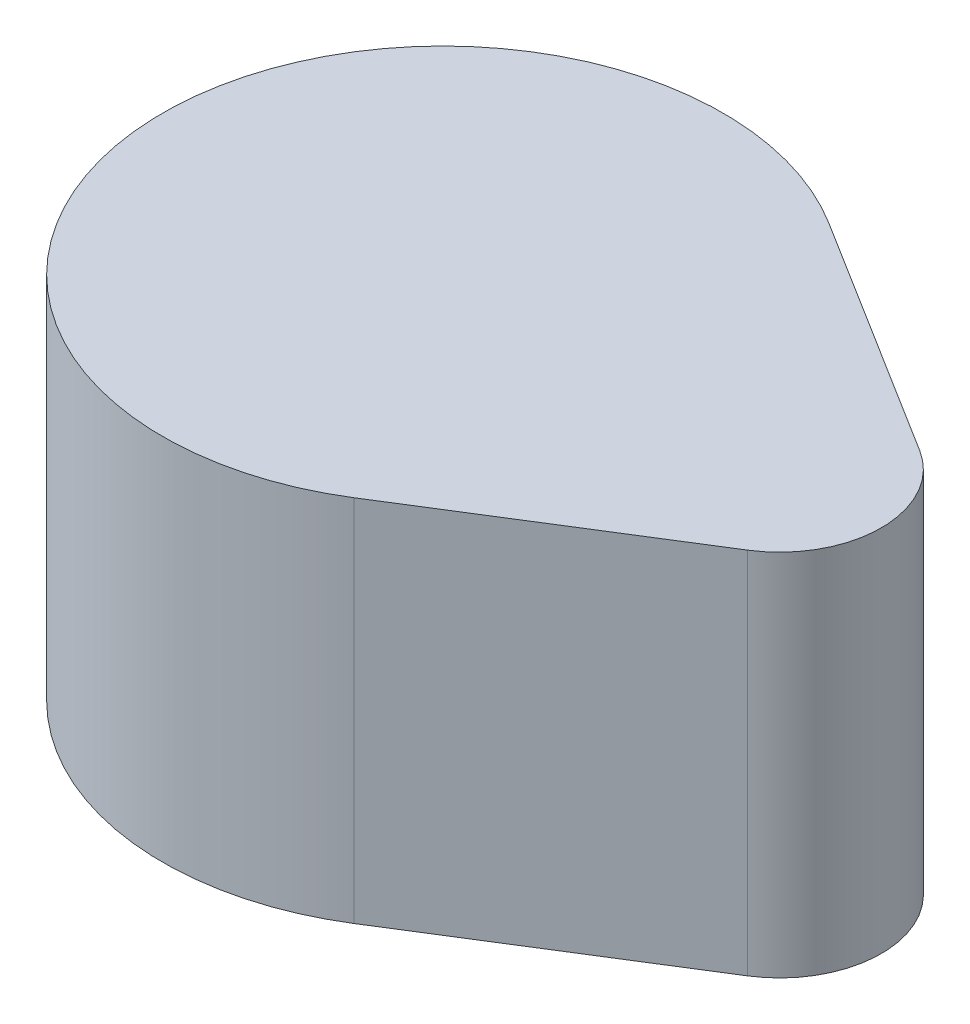
SolidWorks part; units mm, degrees
ref_plane "Front Plane" through (0, 0, 0) normal (0, 0, 1) x (1, 0, 0)
ref_plane "Top Plane" through (0, 0, 0) normal (0, 1, 0) x (1, 0, 0)
ref_plane "Right Plane" through (0, 0, 0) normal (1, 0, 0) x (0, 0, -1)
sketch "Sketch1" plane through (0, 0, 0) normal (0, 1, 0) x (1, 0, 0)
  line L0 (5.1162, 8.1821) -> (13.4556, 2.9676)
  line L1 (5.1162, -8.1821) -> (13.4556, -2.9676)
  line L3 (-9.65, 0) -> (-9.65, -24.75) construction
  line L4 (-9.65, -24.75) -> (15.1, -24.75) construction
  line L5 (15.1, -24.75) -> (15.1, 0) construction
  arc A0 (5.1162, 8.1821) -> (5.1162, -8.1821) centre (0, 0) ccw
  arc A1 (13.4556, -2.9676) -> (13.4556, 2.9676) centre (11.6, 0) ccw
  arc A2 (13.4556, -2.9676) -> (13.4556, 2.9676) centre (11.6, 0) ccw construction
  arc A3 (5.1162, 8.1821) -> (5.1162, -8.1821) centre (0, 0) ccw construction
  circle A5 centre (11.6, 0) radius 3.5 construction
  circle A7 centre (11.6, 0) radius 3.5 construction
  dimension "D1" = 9.65
  dimension "D2" = 24.75
  dimension "D3" = 7
extrude "Boss-Extrude1" add sketch "Sketch1" along normal blind 12.7
ref_axis "Axis1" through (0, 13.335, 0) along (0, -1, 0)
